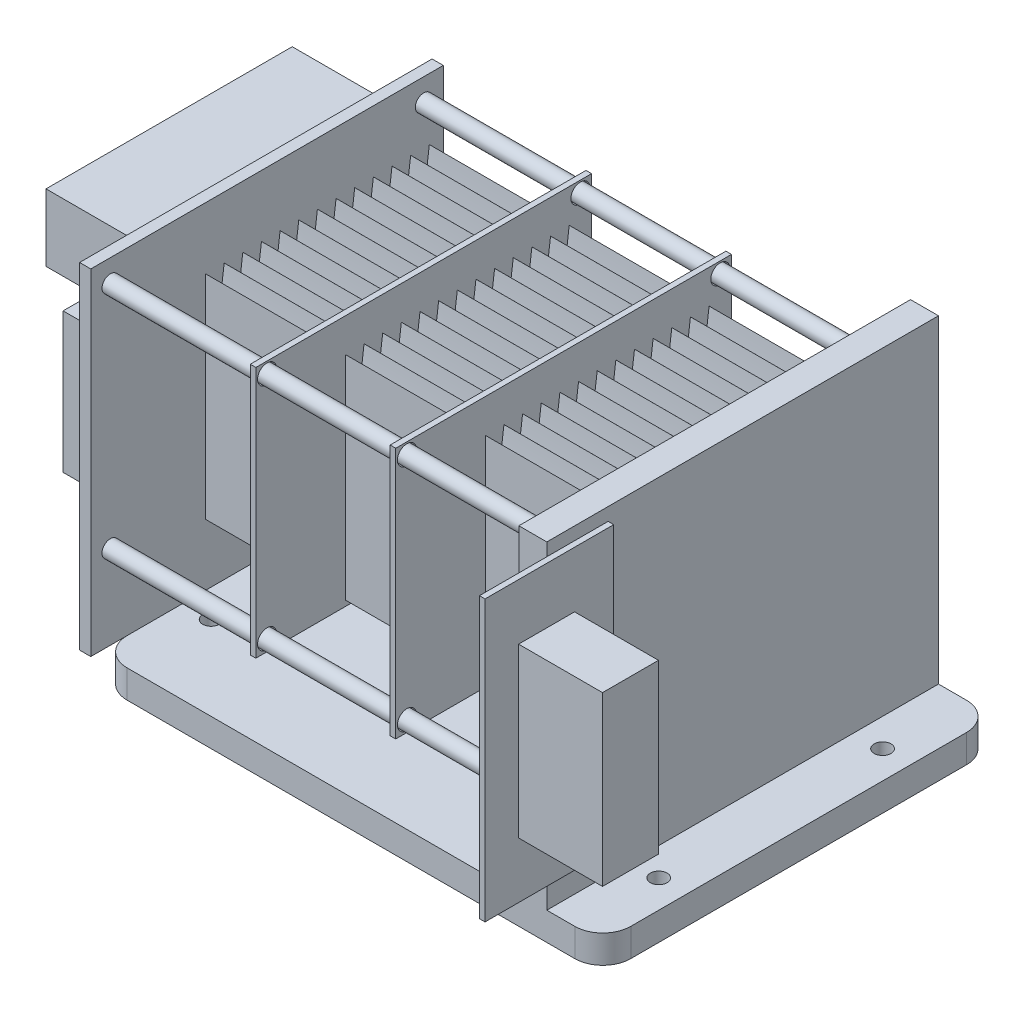
SolidWorks part; units mm, degrees
ref_plane "Front Plane" through (0, 0, 0) normal (0, 0, 1) x (1, 0, 0)
ref_plane "Top Plane" through (0, 0, 0) normal (0, 1, 0) x (1, 0, 0)
ref_plane "Right Plane" through (0, 0, 0) normal (1, 0, 0) x (0, 0, -1)
sketch "Sketch1" plane through (0, 0, 0) normal (0, 1, 0) x (1, 0, 0)
  line L1 (-40, -35) -> (40, -35)
  line L2 (-45, -30) -> (-45, 30)
  line L3 (-40, 35) -> (40, 35)
  line L4 (45, -30) -> (45, 30)
  line L5 (-45, -35) -> (45, 35) construction
  line L6 (-45, 35) -> (45, -35) construction
  arc A0 (-40, -35) -> (-45, -30) centre (-40, -30) cw
  arc A1 (40, -35) -> (45, -30) centre (40, -30) ccw
  arc A2 (40, 35) -> (45, 30) centre (40, 30) cw
  arc A3 (-45, 30) -> (-40, 35) centre (-40, 30) cw
  point P0 (0, 0)
  dimension "D3" = 5
  dimension "D1" = 90
  dimension "D2" = 70
extrude "Boss-Extrude1" add sketch "Sketch1" along normal blind 5
sketch "Sketch2" plane through (0, 5, 0) normal (0, 1, 0) x (1, 0, 0)
  line L0 (30, -35) -> (30, 35)
  line L1 (-40, -35) -> (40, -35) construction
  line L2 (40, 35) -> (-40, 35) construction
  line L3 (30, -35) -> (35, -35)
  line L4 (35, -35) -> (35, 35)
  line L5 (35, 35) -> (30, 35)
  line L6 (45, -30) -> (45, 30) construction
  dimension "D1" = 15
  dimension "D2" = 5
extrude "Boss-Extrude2" add sketch "Sketch2" along normal blind 57
ref_plane "Plane1" through (-50, 0, 0) normal (-1, 0, 0) x (0, 0, 1)
sketch "Sketch3" plane through (-50, 0, 0) normal (-1, 0, 0) x (0, 0, 1)
  line L0 (-30, 0) -> (30, 0) construction
  line L1 (-31.5, 0) -> (31.5, 0)
  line L2 (-31.5, 0) -> (-31.5, 60)
  line L3 (-31.5, 60) -> (31.5, 60)
  line L4 (31.5, 0) -> (31.5, 60)
  line L5 (-35, 5) -> (-35, 0) construction
  dimension "D1" = 63
  dimension "D2" = 60
  dimension "D3" = 0
  dimension "D4" = 3.5
extrude "Boss-Extrude3" add sketch "Sketch3" along normal blind 2 separate body
ref_plane "Plane2" through (28, 0, 0) normal (-1, 0, 0) x (0, 0, 1)
sketch "Sketch4" plane through (28, 0, 0) normal (-1, 0, 0) x (0, 0, 1)
  line L0 (-35, 62) -> (35, 62) construction
  line L1 (30, 13) -> (-30, 13)
  line L2 (30, 13) -> (30, 58)
  line L3 (30, 58) -> (-30, 58)
  line L4 (-30, 13) -> (-30, 58)
  line L5 (30, 13) -> (-30, 58) construction
  line L6 (30, 58) -> (-30, 13) construction
  line L7 (-35, 62) -> (-35, 5) construction
  circle A0 centre (-28, 56) radius 1.7007
  circle A1 centre (-28, 15) radius 1.7007
  circle A2 centre (28, 56) radius 1.7007
  circle A3 centre (28, 15) radius 1.7007
  point P0 (0, 35.5)
  dimension "D1" = 60
  dimension "D2" = 45
  dimension "D3" = 4
  dimension "D4" = 5
  dimension "D5" = 2
  dimension "D6" = 2
  dimension "D7" = 2
  dimension "D8" = 2
  dimension "D9" = 2
  dimension "D10" = 2
  dimension "D11" = 2
  dimension "D12" = 2
extrude "Boss-Extrude4" add sketch "Sketch4" along normal blind 1 separate body
sketch "Sketch6" plane through (27, 0, 0) normal (-1, 0, 0) x (0, 0, 1)
  line L0 (-30, 13) -> (30, 13) construction
  line L1 (-20, 20) -> (20, 20)
  line L2 (-20, 20) -> (-20, 50)
  line L3 (-20, 50) -> (20, 50)
  line L4 (20, 20) -> (20, 50)
  line L5 (-30, 58) -> (-30, 13) construction
  line L6 (30, 13) -> (30, 58) construction
  dimension "D1" = 30
  dimension "D2" = 7
  dimension "D3" = 10
  dimension "D4" = 10
extrude "Boss-Extrude5" add sketch "Sketch6" along normal blind 18 contours L3 L4 L1 L2
sketch "Sketch8" plane through (27, 0, 0) normal (-1, 0, 0) x (0, 0, 1)
  line L0 (-20, 50) -> (-20, 58)
  line L1 (30, 58) -> (-30, 58) construction
  line L2 (20, 50) -> (20, 58)
  line L3 (20, 58) -> (-20, 58)
  line L5 (-20, 50) -> (20, 50) construction
  line L6 (-20, 58) -> (-16.667, 58) construction
  spline S0 degree 2 poles (-20, 58) (-18.3312, 42) (-16.67, 58) knots 0 0 0 1 1 1
  spline S1 degree 2 poles (-16.667, 58) (-14.9982, 42) (-13.337, 58) knots 0 0 0 1 1 1
  spline S2 degree 2 poles (-13.334, 58) (-11.6652, 42) (-10.004, 58) knots 0 0 0 1 1 1
  spline S3 degree 2 poles (-10.001, 58) (-8.3322, 42) (-6.671, 58) knots 0 0 0 1 1 1
  spline S4 degree 2 poles (-6.668, 58) (-4.9992, 42) (-3.338, 58) knots 0 0 0 1 1 1
  spline S5 degree 2 poles (-3.335, 58) (-1.6662, 42) (-0.005, 58) knots 0 0 0 1 1 1
  spline S6 degree 2 poles (-0.002, 58) (1.6668, 42) (3.328, 58) knots 0 0 0 1 1 1
  spline S7 degree 2 poles (3.331, 58) (4.9998, 42) (6.661, 58) knots 0 0 0 1 1 1
  spline S8 degree 2 poles (6.664, 58) (8.3328, 42) (9.994, 58) knots 0 0 0 1 1 1
  spline S9 degree 2 poles (9.997, 58) (11.6658, 42) (13.327, 58) knots 0 0 0 1 1 1
  spline S10 degree 2 poles (13.33, 58) (14.9988, 42) (16.66, 58) knots 0 0 0 1 1 1
  spline S11 degree 2 poles (16.663, 58) (18.3286, 42) (20, 58) knots 0 0 0 1 1 1
  line M7 (30, 58) -> (-30, 58)
  line M10 (-20, 50) -> (20, 50)
  dimension "D2" = 1.667
  dimension "D3" = 3.333
extrude "Boss-Extrude6" add sketch "Sketch8" along normal blind 18 contours S0 L0 M10 | S1 S0 M7 M10 | S2 S1 M7 M10 | S3 S2 M7 M10 | S4 S3 M7 M10 | S5 S4 M7 M10 | S6 S5 M7 M10 | S7 S6 M7 M10 | S8 S7 M7 M10 | S9 S8 M7 M10 | S10 S9 M7 M10 | S11 L3 S10 M10 | S11 L2 M10 region at (27, 52.4005, -19.5831) region at (27, 52.4043, -16.6672) region at (27, 52.4043, -13.3342) region at (27, 52.4043, -10.0012) region at (27, 52.4043, -6.6682) region at (27, 52.4043, -3.3352) region at (27, 52.4043, -0.0022) region at (27, 52.4043, 3.3308) region at (27, 52.4043, 6.6638) region at (27, 52.4043, 9.9968) region at (27, 52.4043, 13.3298) region at (27, 52.4039, 16.6625) region at (27, 52.4003, 19.5824)
pattern_linear "LPattern2" count 3 spacing 25 along (-1, 0, 0) of bodies 111
sketch "Sketch9" plane through (30, 0, 0) normal (-1, 0, 0) x (0, 0, 1)
  circle A0 centre (28, 56) radius 1.5
  circle A1 centre (-28, 56) radius 1.5
  circle A2 centre (-28, 15) radius 1.5
  circle A3 centre (28, 15) radius 1.5
  circle A5 centre (28, 56) radius 1.7007 construction
  circle A6 centre (28, 15) radius 1.7007 construction
  circle A7 centre (-28, 15) radius 1.7007 construction
  dimension "D1" = 3
  dimension "D2" = 0
  dimension "D3" = 0
  dimension "D4" = 0
extrude "Boss-Extrude7" add sketch "Sketch9" along normal up to surface (80 mm away) up to face at (-50, 30, 0)
sketch "Sketch10" plane through (-52, 0, 0) normal (-1, 0, 0) x (0, 0, 1)
  line L1 (-21.5, 59.3949) -> (22.5033, 59.3949)
  line L2 (-21.5, 59.3949) -> (-21.5, 47.3949)
  line L3 (-21.5, 47.3949) -> (22.5033, 47.3949)
  line L4 (22.5033, 59.3949) -> (22.5033, 47.3949)
  line L5 (-31.5, 60) -> (-31.5, 0) construction
  line L7 (-30.8578, 45.2218) -> (-20.8578, 45.2218)
  line L8 (-30.8578, 45.2218) -> (-30.8578, 35.2218)
  line L9 (-30.8578, 35.2218) -> (-20.8578, 35.2218)
  line L10 (-20.8578, 45.2218) -> (-20.8578, 35.2218)
  line L11 (-20.162, 46.9131) -> (-5.162, 46.9131)
  line L12 (-20.162, 46.9131) -> (-20.162, 26.9131)
  line L13 (-20.162, 26.9131) -> (-5.162, 26.9131)
  line L14 (-5.162, 46.9131) -> (-5.162, 26.9131)
  line L15 (-3.6328, 46.8223) -> (11.3672, 46.8223)
  line L16 (-3.6328, 46.8223) -> (-3.6328, 26.8223)
  line L17 (-3.6328, 26.8223) -> (11.3672, 26.8223)
  line L18 (11.3672, 46.8223) -> (11.3672, 26.8223)
  dimension "D1" = 10
  dimension "D2" = 12
  dimension "D4" = 10
  dimension "D5" = 20
  dimension "D6" = 20
  dimension "D7" = 15
  dimension "D8" = 15
extrude "Boss-Extrude9" add sketch "Sketch10" along normal blind 15
sketch "Sketch15" plane through (-52, 0, 0) normal (-1, 0, 0) x (0, 0, 1)
  line L1 (12.4472, 46.9843) -> (27.4472, 46.9843)
  line L2 (12.4472, 46.9843) -> (12.4472, 21.9843)
  line L3 (12.4472, 21.9843) -> (27.4472, 21.9843)
  line L4 (27.4472, 46.9843) -> (27.4472, 21.9843)
  line L5 (-21.2518, 21.3731) -> (23.7482, 21.3731)
  line L6 (-21.2518, 21.3731) -> (-21.2518, 1.3731)
  line L7 (-21.2518, 1.3731) -> (23.7482, 1.3731)
  line L8 (23.7482, 21.3731) -> (23.7482, 1.3731)
  dimension "D1" = 15
  dimension "D2" = 25
  dimension "D3" = 45
  dimension "D4" = 20
extrude "Boss-Extrude10" add sketch "Sketch15" along normal blind 7
sketch "Sketch16" plane through (-52, 0, 0) normal (-1, 0, 0) x (0, 0, 1)
  line L1 (-28.7899, 30.1826) -> (-23.7899, 30.1826)
  line L2 (-28.7899, 30.1826) -> (-28.7899, 15.1826)
  line L3 (-28.7899, 15.1826) -> (-23.7899, 15.1826)
  line L4 (-23.7899, 30.1826) -> (-23.7899, 15.1826)
  dimension "D1" = 5
  dimension "D2" = 15
extrude "Boss-Extrude11" add sketch "Sketch16" along normal blind 15
sketch "Sketch17" plane through (35, 0, 0) normal (1, 0, 0) x (0, 0, -1)
  line L1 (-24.0447, 59.6991) -> (-47.0447, 59.6991)
  line L2 (-24.0447, 59.6991) -> (-24.0447, 9.6991)
  line L3 (-24.0447, 9.6991) -> (-47.0447, 9.6991)
  line L4 (-47.0447, 59.6991) -> (-47.0447, 9.6991)
  dimension "D1" = 23
  dimension "D2" = 50
extrude "Boss-Extrude12" add sketch "Sketch17" along normal blind 1
sketch "Sketch18" plane through (36, 0, 0) normal (1, 0, 0) x (0, 0, -1)
  line L0 (-47.0447, 59.6991) -> (-47.0447, 9.6991) construction
  line L1 (-41.0447, 49.6991) -> (-31.0447, 49.6991)
  line L2 (-41.0447, 49.6991) -> (-41.0447, 19.6991)
  line L3 (-41.0447, 19.6991) -> (-31.0447, 19.6991)
  line L4 (-31.0447, 49.6991) -> (-31.0447, 19.6991)
  line L5 (-24.0447, 59.6991) -> (-47.0447, 59.6991) construction
  dimension "D1" = 30
  dimension "D2" = 10
  dimension "D3" = 6
  dimension "D4" = 10
extrude "Boss-Extrude13" add sketch "Sketch18" along normal blind 15
sketch "Sketch19" plane through (0, 5, 0) normal (0, 1, 0) x (1, 0, 0)
  line L0 (45, -30) -> (45, 30) construction
  line L1 (45, 0) -> (35, 0) construction
  line L2 (35, -35) -> (35, 35) construction
  circle A0 centre (40, 20) radius 1.5
  point P4 (45, 0)
  point P10 (40, 0)
  dimension "D1" = 3
  dimension "D2" = 20
extrude "Cut-Extrude1" cut sketch "Sketch19" against normal through all
mirror "Mirror1" about plane through (0, 0, 0) normal (0, 0, 1) of "Cut-Extrude1"
mirror "Mirror2" about plane through (0, 0, 0) normal (1, 0, 0) of "Mirror1"
